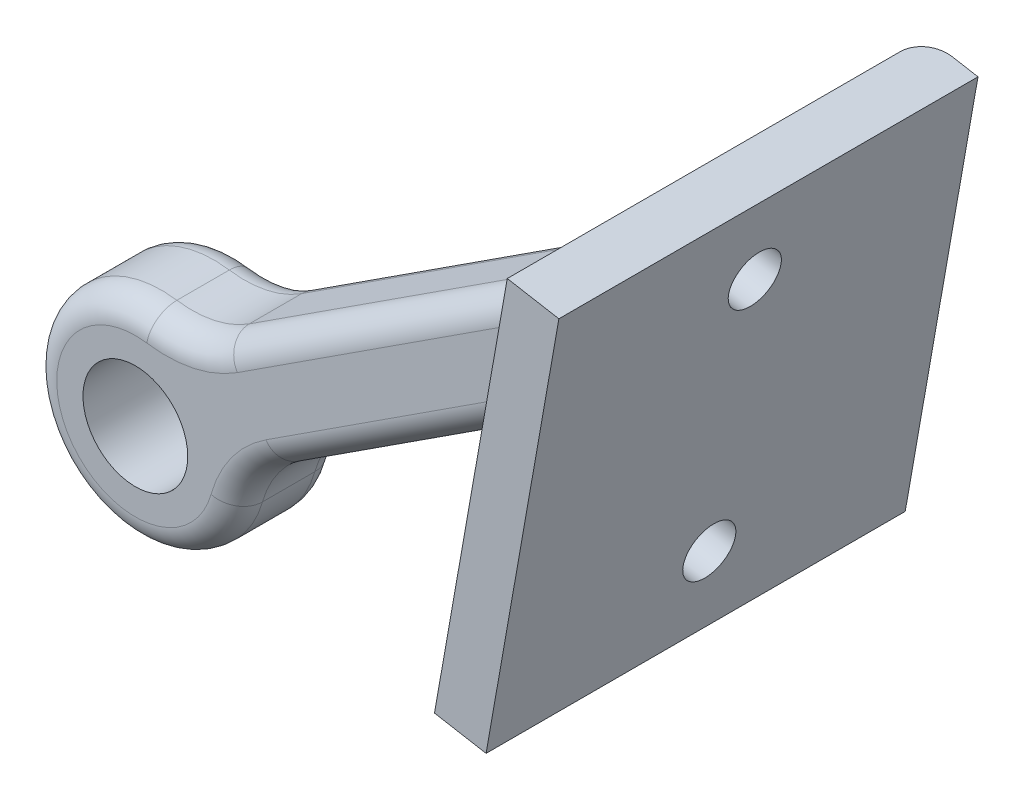
SolidWorks part; units mm, degrees
ref_plane "Front" through (0, 0, 0) normal (0, 0, 1) x (1, 0, 0)
ref_plane "Top" through (0, 0, 0) normal (0, 1, 0) x (1, 0, 0)
ref_plane "Right" through (0, 0, 0) normal (1, 0, 0) x (0, 0, -1)
sketch "Sketch1" plane through (0, 0, 0) normal (0, 0, 1) x (1, 0, 0)
  line L0 (0, 0) -> (25.4, 144.0506) construction
  line L1 (25.4, 144.0506) -> (25.4, 0) construction
  line L2 (25.4, 0) -> (0, 0) construction
  line L3 (4.4107, 25.0141) -> (-1.8429, 26.1168)
  line L4 (-1.8429, 26.1168) -> (6.9785, 76.145)
  line L5 (6.9785, 76.145) -> (13.232, 75.0424)
  line L6 (13.232, 75.0424) -> (4.4107, 25.0141)
  line L7 (-76.2, 0) -> (2.5678, 51.1309) construction
  circle A0 centre (-76.2, 0) radius 12.7
  dimension "D1" = 25.4
  dimension "D2" = 76.2
  dimension "D3" = 50.8
  dimension "D4" = 25.4
  dimension "D5" = 6.35
  dimension "D6" = 10
  dimension "D7" = 25.4
sketch "Sketch2" plane through (0, 0, 0) normal (0, 0, 1) x (1, 0, 0)
  line L0 (-1.8429, 26.1168) -> (6.9785, 76.145) construction
  line L1 (1.0604, 42.5818) -> (4.0752, 59.68)
  line L2 (-56.7711, 12.612) -> (60.7287, 88.8851) construction
  line L3 (-76.2, 0) -> (2.5678, 51.1309) construction
  line L4 (-70.4321, 11.3147) -> (4.0752, 59.68)
  line L5 (-63.5173, 0.6622) -> (1.0604, 42.5818)
  circle A0 centre (-76.2, 0) radius 12.7 construction
  arc A1 (-70.4321, 11.3147) -> (-63.5173, 0.6622) centre (-76.2, 0) ccw
  dimension "D1" = 12.7
extrude "Base-Extrude" add sketch "Sketch2" along normal blind 12.7
sketch "Sketch3" plane through (0, 0, 0) normal (0, 0, 1) x (1, 0, 0)
  line L4 (4.4107, 25.0141) -> (-1.8429, 26.1168)
  line L5 (13.232, 75.0424) -> (4.4107, 25.0141)
  line L6 (6.9785, 76.145) -> (13.232, 75.0424)
  line L7 (-1.8429, 26.1168) -> (6.9785, 76.145)
  line L8 (4.4107, 25.0141) -> (-1.8429, 26.1168)
  line L9 (13.232, 75.0424) -> (4.4107, 25.0141)
  line L10 (6.9785, 76.145) -> (13.232, 75.0424)
  line L11 (-1.8429, 26.1168) -> (6.9785, 76.145)
  dimension "D1" = 0
extrude "Boss-Extrude1" add sketch "Sketch3" along normal blind 50.8
fillet "Fillet1" radius 12.7 2 edges at (-63.5173, 0.6622, 6.35) (-70.4321, 11.3147, 6.35)
sketch "Sketch5" plane through (-6.2535, 1.1027, 0) normal (-0.9848, 0.1736, 0) x (0, 0, 1)
  line L0 (25.4, 76.2) -> (25.4, 25.4) construction
  line L1 (50.8, 76.2) -> (0, 76.2) construction
  line L2 (50.8, 25.4) -> (0, 25.4) construction
  circle A0 centre (25.4, 66.675) radius 3.175
  circle A1 centre (25.4, 34.925) radius 3.175
  dimension "D3" = 6.35
  dimension "D4" = 6.35
  dimension "D1" = 9.525
  dimension "D2" = 9.525
extrude "Cut-Extrude2" cut sketch "Sketch5" against normal through all
fillet "Fillet4" radius 9.525 2 edges at (4.0752, 59.68, 6.35) (1.0604, 42.5818, 6.35)
fillet "Fillet5" radius 3.175 15 edges at (3.3566, 60.1558, 12.7) (-7.6778, 32.3485, 0) (-32.4826, 35.9491, 12.7) (-37.4064, 17.6117, 0) (-69.7784, 12.717, 12.7) (-61.9703, 0.6885, 0) (-86.8524, -6.9149, 12.7) (-86.8524, -6.9149, 0) (5.8865, 69.9524, 0) (-61.9703, 0.6885, 12.7) (-7.6778, 32.3485, 12.7) (-69.7784, 12.717, 0) (3.3566, 60.1558, 0) (-37.4064, 17.6117, 12.7) (-32.4826, 35.9491, 0)
sketch "Sketch6" plane through (0, 0, 12.7) normal (0, 0, 1) x (1, 0, 0)
  circle A0 centre (-76.2, 0) radius 6.35
  dimension "D1" = 12.7
extrude "Cut-Extrude3" cut sketch "Sketch6" against normal through all
fillet "Fillet6" radius 1.5875 3 edges at (-1.6488, 27.2176, 11.3088) (3.8228, 58.2485, 12.236) (1.195, 43.3451, 12.7)
